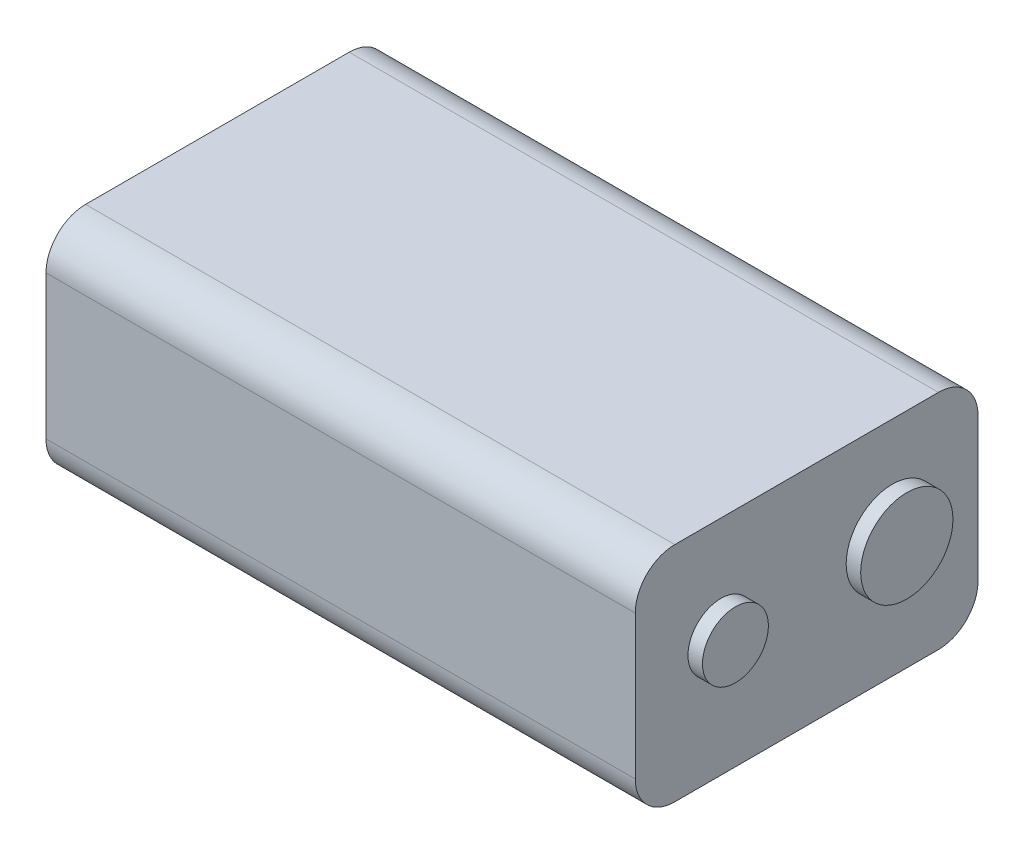
SolidWorks part; units mm, degrees
ref_plane "Front Plane" through (0, 0, 0) normal (0, 0, 1) x (1, 0, 0)
ref_plane "Top Plane" through (0, 0, 0) normal (0, 1, 0) x (1, 0, 0)
ref_plane "Right Plane" through (0, 0, 0) normal (1, 0, 0) x (0, 0, -1)
sketch "Sketch1" plane through (0, 0, 0) normal (0, 1, 0) x (1, 0, 0)
  line L1 (-21.9474, 18.298) -> (22.7526, 18.298)
  line L2 (-21.9474, 18.298) -> (-21.9474, -7.702)
  line L3 (-21.9474, -7.702) -> (22.7526, -7.702)
  line L4 (22.7526, 18.298) -> (22.7526, -7.702)
  dimension "D1" = 44.7
  dimension "D2" = 26
extrude "Boss-Extrude1" add sketch "Sketch1" along normal blind 16.9
fillet "Fillet1" radius 3 4 edges at (0.4026, 16.9, -18.298) (0.4026, 0, -18.298) (0.4026, 0, 7.702) (0.4026, 16.9, 7.702)
sketch "Sketch2" plane through (22.7526, 0, 0) normal (1, 0, 0) x (0, 0, -1)
  line L4 (-7.702, 13.9) -> (-7.702, 3) construction
  circle A0 centre (11.798, 9.1182) radius 3.5
  circle A1 centre (-1.202, 9.1182) radius 2.5
  point P4 (0, 0)
  point P5 (-1.4338, 9.2101)
  point P6 (0, 0)
  point P7 (0, 0)
  point P8 (0, 0)
  point P9 (0, 0)
  point P10 (-2.1677, 9.1182)
  point P15 (0, 0)
  dimension "D3" = 5
  dimension "D4" = 7
  dimension "D1" = 13
  dimension "D2" = 6.5
extrude "Boss-Extrude2" add sketch "Sketch2" along normal blind 1.1
